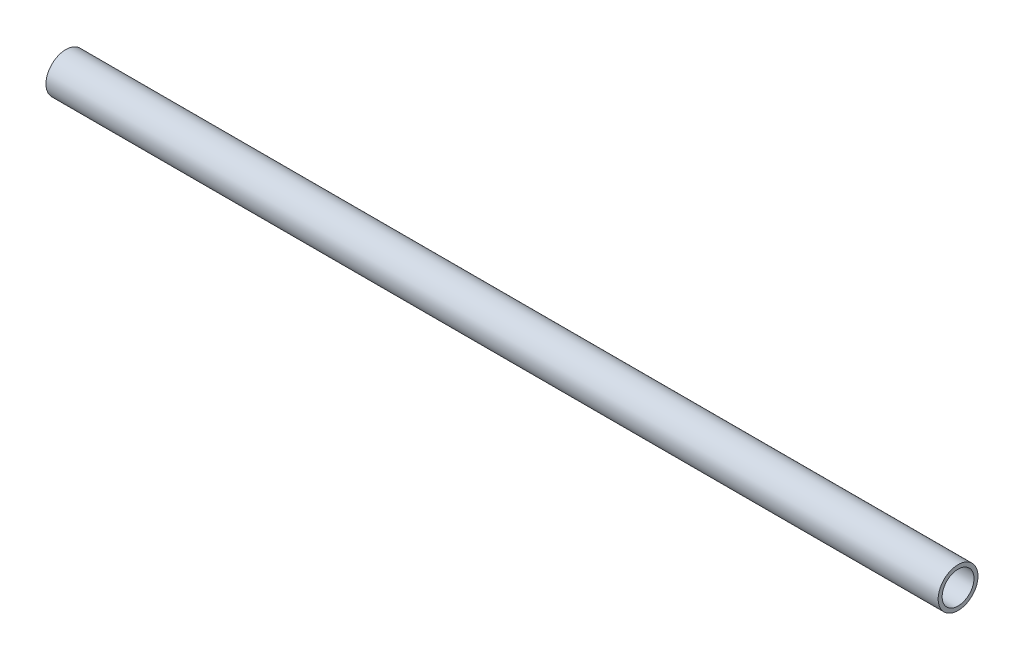
SolidWorks part; units mm, degrees
material "Acrylic (Medium-high impact)"
ref_plane "Front" through (0, 0, 0) normal (0, 0, 1) x (1, 0, 0)
ref_plane "Top" through (0, 0, 0) normal (0, 1, 0) x (1, 0, 0)
ref_plane "Right" through (0, 0, 0) normal (1, 0, 0) x (0, 0, -1)
sketch "Sketch1" plane through (0, 0, 0) normal (1, 0, 0) x (0, 0, -1)
  circle A0 centre (0, 0) radius 15.875
  circle A1 centre (0, 0) radius 12.7
  point P4 (15.875, 0)
  point P5 (12.7, 0)
  dimension "OD" = 31.75
  dimension "ID" = 25.4
  dimension "Wall" = 3.175
extrude "Extrude1" add sketch "Sketch1" along normal mid plane 711.2
